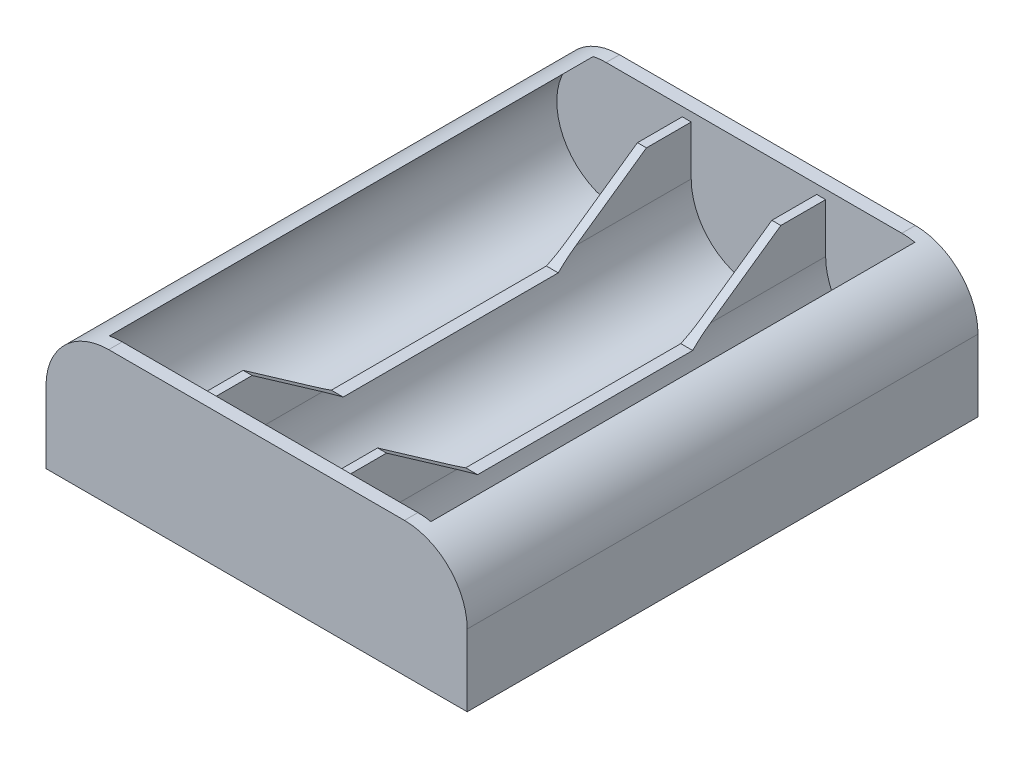
SolidWorks part; units mm, degrees
ref_plane "Front Plane" through (0, 0, 0) normal (0, 0, 1) x (1, 0, 0)
ref_plane "Top Plane" through (0, 0, 0) normal (0, 1, 0) x (1, 0, 0)
ref_plane "Right Plane" through (0, 0, 0) normal (1, 0, 0) x (0, 0, -1)
sketch "Sketch1" plane through (0, 0, 0) normal (0, 1, 0) x (1, 0, 0)
  line L0 (0, 0) -> (0, -55.5)
  line L2 (47, -55.5) -> (47, 0)
  line L3 (47, 0) -> (0, 0)
  line L5 (0, -55.5) -> (47, -55.5)
extrude "Boss-Extrude1" add sketch "Sketch1" along normal blind 15
sketch "Sketch2" plane through (0, 0, 55.5) normal (0, 0, 1) x (1, 0, 0)
  line L0 (0, 15) -> (47, 15) construction
  line L1 (0, 15) -> (47, 15)
  line L2 (0, 15) -> (0, 0)
  line L3 (0, 0) -> (47, 0)
  line L4 (47, 15) -> (47, 0)
  line L5 (0, 15) -> (0, 0) construction
  circle A0 centre (8.5, 8.5) radius 7
  circle A1 centre (23.5, 8.5) radius 7
  circle A2 centre (38.5, 8.5) radius 7
extrude "Cut-Extrude4" cut sketch "Sketch2" against normal blind 54 contours L1 A0 | L1 A1 | L1 A2 region at (8.5, 8.4232, 55.5) region at (23.5, 8.4232, 55.5) region at (38.5, 8.4232, 55.5)
fillet "Fillet1" radius 7 1 edges at (47, 15, 27.75) type face fillet first side face at (23.5, 15, 28.3125) second side face at (47, 7.5, 27.75)
fillet "Fillet2" radius 7 1 edges at (0, 15, 27.75) type face fillet first side face at (19.986, 15, 24.4286) second side face at (0, 7.5, 27.75)
sketch "Sketch3" plane through (0, 0, 55.5) normal (0, 0, 1) x (1, 0, 0)
  line L0 (30.5, 8.5) -> (30.5, 15)
  line L1 (26.0981, 15) -> (35.9019, 15) construction
  line L3 (26.0981, 15) -> (26.0981, 8.5)
  line L4 (26.0981, 8.5) -> (30.5, 8.5)
  line L5 (35.9019, 8.5) -> (35.9019, 15)
  line L6 (35.9019, 15) -> (31.5, 15)
  line L7 (31.5, 8.5) -> (31.5, 15)
  line L8 (30.5, 15) -> (26.0981, 15)
  line L9 (31.5, 8.5) -> (35.9019, 8.5)
  line L11 (15.5, 8.5) -> (11.0981, 8.5)
  line L12 (16.5, 15) -> (20.9019, 15)
  line L13 (15.5, 8.5) -> (15.5, 15)
  line L14 (11.0981, 15) -> (15.5, 15)
  line L15 (11.0981, 8.5) -> (11.0981, 15)
  line L16 (20.9019, 8.5) -> (16.5, 8.5)
  line L17 (20.9019, 15) -> (20.9019, 8.5)
  line L18 (16.5, 8.5) -> (16.5, 15)
  arc A1 (20.9019, 15) -> (26.0981, 15) centre (23.5, 8.5) ccw construction
  arc A2 (35.9019, 15) -> (41.4494, 14.8483) centre (38.5, 8.5) ccw construction
extrude "Cut-Extrude5" cut sketch "Sketch3" against normal blind 54
sketch "Sketch4" plane through (0, 0, 55.5) normal (0, 0, 1) x (1, 0, 0)
  line L0 (15.5, 15) -> (15.5, 14)
  line L2 (15.5, 14) -> (16.5, 14)
  line L3 (16.5, 15) -> (16.5, 8.5) construction
  line L4 (16.5, 14) -> (16.5, 15)
  line L5 (16.5, 15) -> (15.5, 15)
  line L6 (16.5, 15) -> (30.5, 15) construction
  line L7 (23.5, 15) -> (23.5, 12.7021)
  line L8 (30.5, 14) -> (30.5, 15)
  line L9 (31.5, 14) -> (30.5, 14)
  line L10 (31.5, 15) -> (31.5, 14)
  line L11 (30.5, 15) -> (31.5, 15)
  line M7 (16.5, 15) -> (15.5, 15)
  line M8 (15.5, 15) -> (15.5, 8.5)
  line M16 (31.5, 8.5) -> (31.5, 15)
  line M17 (31.5, 15) -> (30.5, 15)
  line M18 (30.5, 15) -> (30.5, 8.5)
  line M20 (16.5, 8.5) -> (16.5, 15)
extrude "Cut-Extrude6" cut sketch "Sketch4" against normal blind 54 contours L2 M8 M20 M7 | L9 M16 M17 M18 region at (16, 14.5, 55.5) region at (31, 14.5, 55.5)
sketch "Sketch5" plane through (15.5, 0, 0) normal (-1, 0, 0) x (0, 0, 1)
  line L0 (6.5, 14) -> (50.5, 14)
  line L1 (1.5, 14) -> (55.5, 14) construction
  line L4 (6.5, 14) -> (16.5, 7)
  line L5 (28.5, 14) -> (28.5, 8.5) construction
  line L6 (1.5, 8.5) -> (55.5, 8.5) construction
  line L9 (50.5, 14) -> (40.5, 7)
  line L10 (40.5, 7) -> (16.5, 7)
extrude "Cut-Extrude7" cut sketch "Sketch5" against normal blind 20
extrude "Cut-Extrude8" cut sketch "Sketch5<2>" along normal blind 5
sketch "Sketch5<2>" plane through (15.5, 0, 0) normal (-1, 0, 0) x (0, 0, 1) same geometry as "Sketch5"
sketch "Sketch6" plane through (0, 0, 55.5) normal (0, 0, 1) x (1, 0, 0)
  line L0 (0, 0) -> (47, 0)
  line L1 (47, 0) -> (47, 8)
  line L2 (40, 15) -> (7, 15)
  line L3 (0, 8) -> (0, 0)
  arc A0 (47, 8) -> (40, 15) centre (40, 8) ccw
  arc A2 (7, 15) -> (0, 8) centre (7, 8) ccw
extrude "Boss-Extrude3" add sketch "Sketch6" along normal blind 1.5
